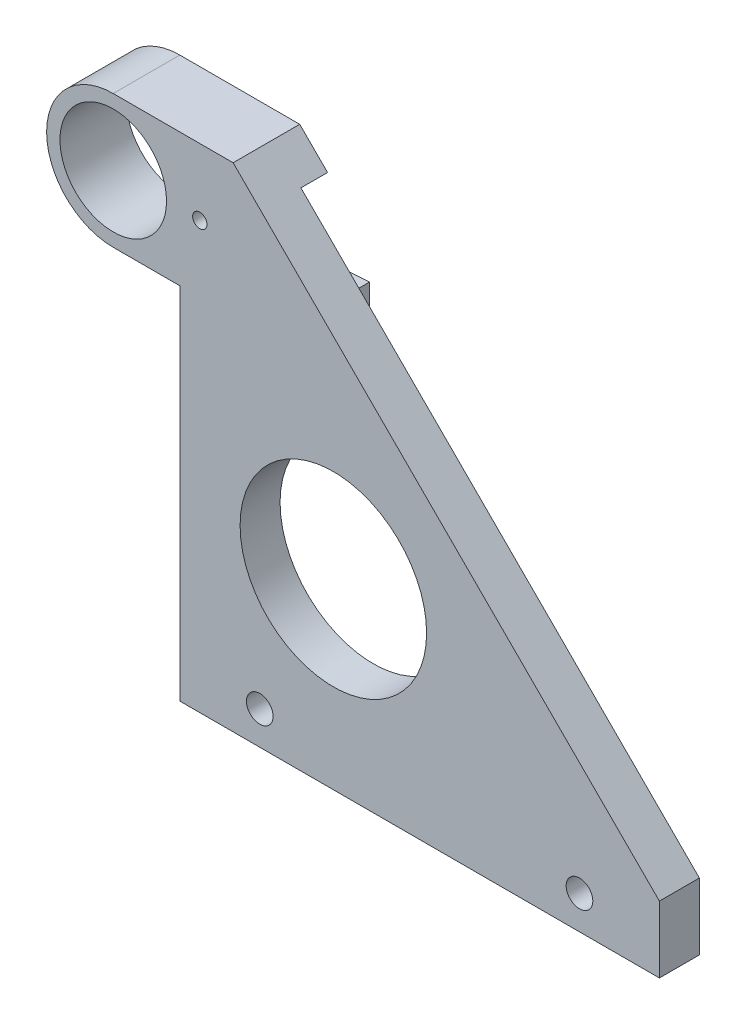
SolidWorks part; units mm, degrees
ref_plane "前视基准面" through (0, 0, 0) normal (0, 0, 1) x (1, 0, 0)
ref_plane "上视基准面" through (0, 0, 0) normal (0, 1, 0) x (1, 0, 0)
ref_plane "右视基准面" through (0, 0, 0) normal (1, 0, 0) x (0, 0, -1)
sketch "草图1" plane through (0, 0, 0) normal (0, 0, 1) x (1, 0, 0)
  line L0 (-18, 0) -> (18, 0)
  line L1 (18, 0) -> (18, 5)
  line L2 (18, 5) -> (-14, 37)
  line L3 (-14, 37) -> (-28, 37)
  line L4 (-28, 37) -> (-28, 27)
  line L5 (-28, 27) -> (-18, 27)
  line L6 (-18, 27) -> (-18, 0)
  point P3 (-28, 32)
  point P4 (0, 0)
  dimension "D1" = 36
  dimension "D2" = 5
  dimension "D3" = 10
  dimension "D4" = 27
  dimension "D5" = 135
extrude "凸台-拉伸1" add sketch "草图1" along normal blind 3
sketch "草图3" plane through (0, 0, 3) normal (0, 0, 1) x (1, 0, 0)
  circle A0 centre (-6.4764, 13.6875) radius 7
  dimension "D1" = 14
extrude "切除-拉伸1" cut sketch "草图3" against normal through all
sketch "草图4" plane through (0, 0, 3) normal (0, 0, 1) x (1, 0, 0)
  line L0 (-18, 5) -> (18, 0) construction
  line L1 (-18, 0) -> (18, 0) construction
  line L2 (-18, 0) -> (-18, 5) construction
  line L3 (-18, 5) -> (18, 5) construction
  line L4 (18, 0) -> (18, 5) construction
  line L5 (18, 5) -> (-18, 0) construction
  line L6 (-1000, 2.5) -> (49000, 2.5) construction
  line L7 (0, -997.5) -> (0, 49002.5) construction
  circle A0 centre (12, 2.5) radius 1
  circle A1 centre (-12, 2.5) radius 1
  point P9 (0, 2.5)
  dimension "D1" = 2
  dimension "D2" = 12
extrude "切除-拉伸2" cut sketch "草图4" against normal through all
fillet "圆角1" 2 edges at (-28, 37, 1.5) (-28, 27, 1.5) type full round first side face at (-21, 37, 1.5) second side face at (-23, 27, 1.5) middle face at (-28, 32, 1.5)
sketch "草图6" plane through (0, 0, 0) normal (0, 0, -1) x (-1, 0, 0)
  line L0 (23, 37) -> (14, 37)
  line L1 (14, 37) -> (8.7699, 31.7699)
  line L2 (-18, 5) -> (14, 37) construction
  line L3 (8.7699, 31.7699) -> (8.7699, 27)
  line L4 (8.7699, 27) -> (23, 27)
  arc A0 (23, 27) -> (23, 37) centre (23, 32) ccw
extrude "凸台-拉伸2" add sketch "草图6" along normal blind 2
sketch "草图7" plane through (0, 0, 3) normal (0, 0, 1) x (1, 0, 0)
  circle A0 centre (-23, 32) radius 4
  dimension "D1" = 8
extrude "切除-拉伸3" cut sketch "草图7" against normal through all
sketch "草图8" plane through (0, 0, -2) normal (0, 0, -1) x (-1, 0, 0)
  line L0 (20.9747, 35.4494) -> (20.9747, 28.5506)
  line L1 (20.9747, 28.5506) -> (7.0213, 29.4729)
  line L2 (7.0213, 29.4729) -> (7.0213, 34.6187)
  line L3 (7.0213, 34.6187) -> (20.9747, 35.4494)
  circle A0 centre (23, 32) radius 4 construction
extrude "切除-拉伸4" cut sketch "草图8" against normal up to surface (2 mm away) up to face at (-2.9233, 15.1283, 0)
sketch "草图9" plane through (0, 0, 0) normal (0, 0, -1) x (-1, 0, 0)
  circle A0 centre (16.5, 32) radius 0.5371
  arc A1 (20.9747, 35.4494) -> (20.9747, 28.5506) centre (23, 32) ccw construction
  circle A2 centre (23, 32) radius 4 construction
  point P6 (19, 32)
  dimension "D1" = 6.5
extrude "切除-拉伸5" cut sketch "草图9" against normal through all
sketch "草图10" plane through (0, 0, 0) normal (0, 0, -1) x (-1, 0, 0)
  circle A0 centre (12, 2.5) radius 1.85
  circle A1 centre (-12, 2.5) radius 1.85
  dimension "D1" = 3.7
extrude "切除-拉伸6" cut sketch "草图10" against normal blind 1.5
